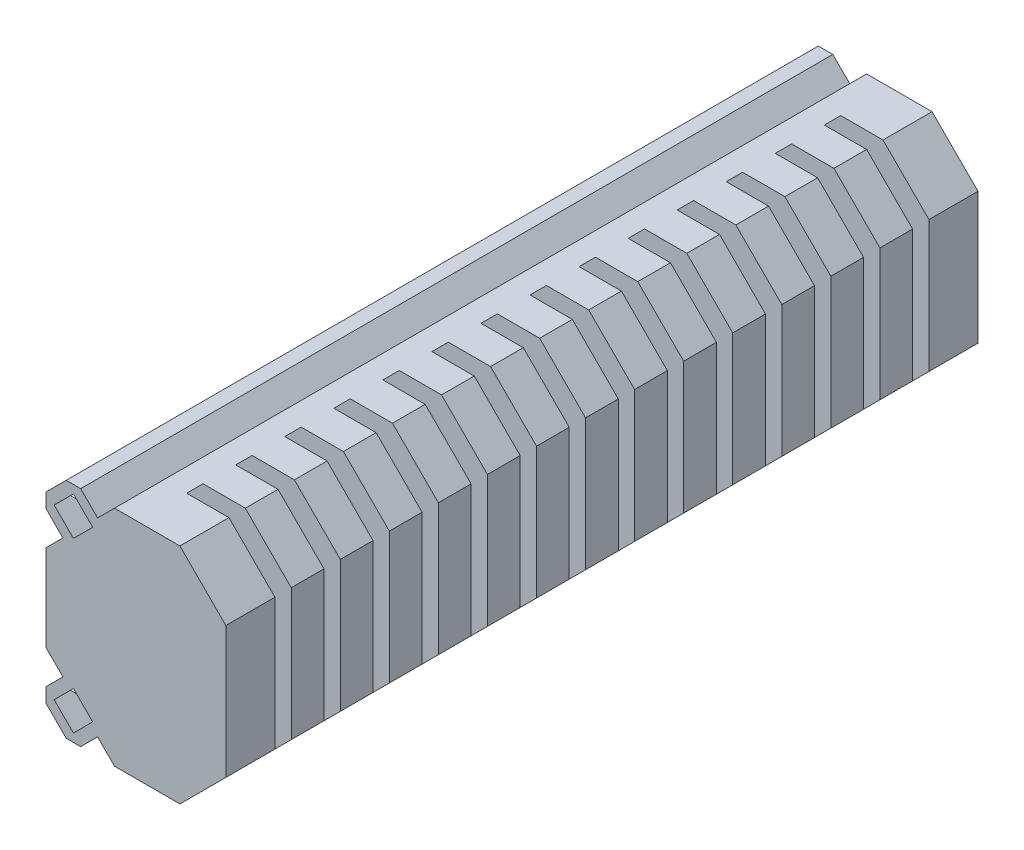
SolidWorks part; units mm, degrees
ref_plane "Ebene vorne" through (0, 0, 0) normal (0, 0, 1) x (1, 0, 0)
ref_plane "Ebene oben" through (0, 0, 0) normal (0, 1, 0) x (1, 0, 0)
ref_plane "Ebene rechts" through (0, 0, 0) normal (1, 0, 0) x (0, 0, -1)
sketch "Skizze3" plane through (0, 0, 0) normal (0, 0, 1) x (1, 0, 0)
  line L0 (-7, 0) -> (0, 7) construction
  line L1 (0, 7) -> (0, -7) construction
  line L2 (0, -7) -> (-7, 0) construction
  line L3 (-7.5, 0) -> (49992.5, 0) construction
  line L4 (-8.2, -3.1716) -> (-8.2, 3.1716)
  line L5 (-8.2, 3.1716) -> (-3.1716, 8.2)
  line L6 (-3.1716, 8.2) -> (1.6284, 8.2)
  line L7 (1.6284, 8.2) -> (5, 4.8284)
  line L13 (0, 7) -> (3, 4) construction
  line L14 (3, 4) -> (3, -4) construction
  line L15 (3, -4) -> (0, -7) construction
  line L16 (5, 4.8284) -> (5, -4.8284)
  line L17 (-8.2, -3.1716) -> (-3.1716, -8.2)
  line L18 (-3.1716, -8.2) -> (1.6284, -8.2)
  line L19 (1.6284, -8.2) -> (5, -4.8284)
  point P20 (-8.2, 0)
  point P23 (5, 0)
  dimension "D2" = 45
  dimension "D3" = 2
  dimension "D4" = 3
  dimension "D5" = 14
  dimension "D1" = 1.2
  dimension "D6" = 2
  dimension "D7" = 1.2
  dimension "D8" = 4.8
extrude "Aufsatz-Linear austragen2" add sketch "Skizze3" along normal mid plane 2.4
sketch "Skizze2" plane through (0, 0, 0) normal (0, 0, 1) x (1, 0, 0)
  line L0 (-7, 0) -> (0, 7)
  line L1 (0, 7) -> (0, -7) construction
  line L2 (0, -7) -> (-7, 0)
  line L3 (-7.5, 0) -> (49992.5, 0) construction
  line L13 (0, 7) -> (3, 4)
  line L14 (3, 4) -> (3, -4)
  line L15 (3, -4) -> (0, -7)
  point P10 (3.1883, -3.4537)
  dimension "D2" = 45
  dimension "D4" = 3
  dimension "D5" = 14
extrude "Schnitt-Linear austragen1" cut sketch "Skizze2" against normal mid plane 0.8
sketch "Skizze5" plane through (0, 0, 0) normal (0, 0, 1) x (1, 0, 0)
  line L0 (-7, 0) -> (-6.1515, 0.8485)
  line L1 (-6.1515, 0.8485) -> (-5.3029, 0)
  line L2 (-5.3029, 0) -> (-6.1515, -0.8485)
  line L3 (-6.1515, -0.8485) -> (-7, 0)
  line L5 (-7, 0) -> (0, -7)
  line L6 (0, -7) -> (3, -4)
  line L7 (3, -4) -> (3, 4)
  line L8 (3, 4) -> (0, 7)
  line L9 (0, 7) -> (-7, 0)
  line L10 (-7, 0) -> (0, -7) construction
  line L11 (0, -7) -> (3, -4) construction
  line L12 (3, -4) -> (3, 4) construction
  line L13 (3, 4) -> (0, 7) construction
  line L14 (0, 7) -> (-7, 0) construction
  point P2 (-5.3661, 0)
  dimension "D2" = 1.2
  dimension "D1" = 0
extrude "Schnitt-Linear austragen2" cut sketch "Skizze5" against normal through all both and the other way through all
sketch "Skizze6" plane through (0, 0, 1.2) normal (0, 0, 1) x (1, 0, 0)
  line L0 (0, 0) -> (50000, 0) construction
  line L1 (1.6284, 8.2) -> (-3.1716, 8.2) construction
  line L3 (-3.1716, 8.2) -> (-8.2, 3.1716) construction
  line L4 (-1.4745, 8.2) -> (-3.1716, 8.2)
  line L5 (-8.2, 3.1716) -> (-8.2, -3.1716)
  line L6 (-3.1716, 8.2) -> (-8.2, 3.1716)
  line L7 (-4.5029, -5.1716) -> (-4.5029, 5.1716)
  line L8 (-4.5029, 5.1716) -> (-1.4745, 8.2)
  line L9 (-8.2, 3.1716) -> (-8.2, -3.1716) construction
  line L10 (-4.5029, -5.1716) -> (-1.4745, -8.2)
  line L11 (-3.1716, -8.2) -> (-8.2, -3.1716)
  line L12 (-1.4745, -8.2) -> (-3.1716, -8.2)
  point P11 (-4.5029, 0)
  point P14 (-8.2, 0)
  dimension "D1" = 1.2
  dimension "D2" = 0.8
extrude "Aufsatz-Linear austragen3" add sketch "Skizze6" along normal blind 1.2
sketch "Skizze7" plane through (0, 0, -1.2) normal (0, 0, -1) x (-1, 0, 0)
  line L4 (6.1515, -0.8485) -> (7, 0)
  line L5 (7, 0) -> (6.1515, 0.8485)
  line L6 (6.1515, 0.8485) -> (5.3029, 0)
  line L7 (5.3029, 0) -> (6.1515, -0.8485)
  line L8 (6.1515, -0.8485) -> (7, 0)
  line L9 (7, 0) -> (6.1515, 0.8485)
  line L10 (6.1515, 0.8485) -> (5.3029, 0)
  line L11 (5.3029, 0) -> (6.1515, -0.8485)
  dimension "D1" = 0
extrude "Schnitt-Linear austragen3" cut sketch "Skizze7" against normal through all
pattern_linear "Lineares Muster1" count 15 spacing 3.6 along (0, 0, 1) of "Aufsatz-Linear austragen2", "Schnitt-Linear austragen1", "Schnitt-Linear austragen2", "Aufsatz-Linear austragen3", "Schnitt-Linear austragen3"
sketch "Skizze8" plane through (0, 0, -1.2) normal (0, 0, -1) x (-1, 0, 0)
  line L8 (3.1716, -8.2) -> (8.2, -3.1716)
  line L9 (8.2, -3.1716) -> (8.2, 3.1716)
  line L10 (8.2, 3.1716) -> (3.1716, 8.2)
  line L11 (3.1716, 8.2) -> (-1.6284, 8.2)
  line L12 (-1.6284, 8.2) -> (-5, 4.8284)
  line L13 (-5, 4.8284) -> (-5, -4.8284)
  line L14 (-5, -4.8284) -> (-1.6284, -8.2)
  line L15 (-1.6284, -8.2) -> (3.1716, -8.2)
  line L16 (3.1716, -8.2) -> (8.2, -3.1716)
  line L17 (8.2, -3.1716) -> (8.2, 3.1716)
  line L18 (8.2, 3.1716) -> (3.1716, 8.2)
  line L19 (3.1716, 8.2) -> (-1.6284, 8.2)
  line L20 (-1.6284, 8.2) -> (-5, 4.8284)
  line L21 (-5, 4.8284) -> (-5, -4.8284)
  line L22 (-5, -4.8284) -> (-1.6284, -8.2)
  line L23 (-1.6284, -8.2) -> (3.1716, -8.2)
  dimension "D1" = 0
extrude "Aufsatz-Linear austragen4" add sketch "Skizze8" along normal blind 1.2 and the other way blind 0.8
sketch "Skizze9" plane through (0, 0, 51.6) normal (0, 0, 1) x (1, 0, 0)
  line L0 (-1.4745, 8.2) -> (-3.1716, 8.2) construction
  line L1 (-3.1716, 8.2) -> (-8.2, 3.1716) construction
  line L2 (-8.2, 3.1716) -> (-8.2, -3.1716) construction
  line L3 (-8.2, -3.1716) -> (-3.1716, -8.2) construction
  line L4 (-3.1716, -8.2) -> (-1.4745, -8.2) construction
  line L5 (-1.4745, 8.2) -> (-3.1716, 8.2)
  line L6 (-3.1716, 8.2) -> (-8.2, 3.1716)
  line L7 (-8.2, 3.1716) -> (-8.2, -3.1716)
  line L8 (-1.4745, 8.2) -> (-4.5029, 5.1716)
  line L9 (-4.5029, 5.1716) -> (-4.5029, -5.1716)
  line L10 (-4.5029, -5.1716) -> (-1.4745, -8.2)
  line L11 (-1.4745, -8.2) -> (1.6284, -8.2)
  line L12 (1.6284, -8.2) -> (5, -4.8284)
  line L13 (5, -4.8284) -> (5, 4.8284)
  line L14 (5, 4.8284) -> (1.6284, 8.2)
  line L15 (1.6284, 8.2) -> (-1.4745, 8.2)
  line L19 (-1.4745, -8.2) -> (1.6284, -8.2)
  line L20 (1.6284, -8.2) -> (5, -4.8284)
  line L21 (5, -4.8284) -> (5, 4.8284)
  line L22 (5, 4.8284) -> (1.6284, 8.2)
  line L23 (1.6284, 8.2) -> (-1.4745, 8.2)
  line L24 (-8.2, -3.1716) -> (-3.1716, -8.2)
  line L25 (-3.1716, -8.2) -> (-1.4745, -8.2)
  dimension "D1" = 0
extrude "Aufsatz-Linear austragen5" add sketch "Skizze9" along normal blind 1.2 and the other way blind 0.8
sketch "Skizze10" plane through (0, 0, -2.4) normal (0, 0, -1) x (-1, 0, 0)
  line L0 (2.1631, -8.2) -> (50002.1631, -8.2) construction
  line L1 (8.2, -2.1493) -> (8.2, -50002.1493) construction
  line L2 (6.1858, -7.6) -> (7.6, -6.1858)
  line L3 (7.6, -6.1858) -> (6.3929, -4.9787)
  line L6 (4.413, -6.9586) -> (5.6544, -8.2)
  line L7 (3.1716, -8.2) -> (8.2, -3.1716) construction
  line L8 (5.6544, -8.2) -> (6.7172, -8.2)
  line L9 (6.7172, -8.2) -> (8.2, -6.7172)
  line L10 (8.2, -6.7172) -> (8.2, -5.6544)
  line L11 (8.2, -5.6544) -> (6.9586, -4.413)
  line L12 (4.413, -6.9586) -> (4.9787, -6.3929)
  line L13 (4.7716, -6.1858) -> (4.2059, -6.7515) construction
  line L14 (7.6, -6.1858) -> (8.1657, -6.7515) construction
  line L15 (6.1858, -4.7716) -> (6.7515, -4.2059) construction
  line L16 (6.9586, -4.413) -> (6.3929, -4.9787)
  line L17 (4.9787, -6.3929) -> (4.7716, -6.1858) construction
  line L18 (4.7716, -6.1858) -> (6.1858, -4.7716) construction
  line L19 (6.1858, -4.7716) -> (6.3929, -4.9787) construction
  line L20 (6.8929, -6.8929) -> (5.4787, -5.4787) construction
  line L21 (4.9787, -6.3929) -> (6.1858, -7.6)
  point P14 (0, 0)
  point P26 (6.7515, -4.2059)
  dimension "D1" = 2
  dimension "D2" = 0.6
  dimension "D3" = 0.6
  dimension "D4" = 0.8
extrude "Aufsatz-Linear austragen6" add sketch "Skizze10" against normal up to surface (55.2 mm away)
sketch "Skizze12" plane through (0, 0, -2.4) normal (0, 0, -1) x (-1, 0, 0)
  line L0 (6.1858, -7.6) -> (4.9787, -6.3929) construction
  line L1 (7.6, -6.1858) -> (6.1858, -7.6) construction
  line L2 (6.3929, -4.9787) -> (7.6, -6.1858) construction
  line L3 (6.1858, -7.6) -> (4.7716, -6.1858)
  line L4 (7.6, -6.1858) -> (6.1858, -7.6)
  line L5 (6.1858, -4.7716) -> (7.6, -6.1858)
  line L6 (6.1858, -4.7716) -> (4.7716, -6.1858)
extrude "Schnitt-Linear austragen5" cut sketch "Skizze12" against normal through all
mirror "Spiegeln1" about plane through (0, 0, 0) normal (0, 1, 0) of "Schnitt-Linear austragen5", "Aufsatz-Linear austragen6"
sketch "Skizze11" plane through (-8.2, 0, 0) normal (-1, 0, 0) x (0, 0, 1)
  line L3 (52.8, 4.7716) -> (-2.4, 4.7716) construction
  line L4 (52.8, 7.6) -> (-2.4, 7.6) construction
  line L5 (52.8, 6.1858) -> (-2.4, 6.1858) construction
  line L6 (-1.2, 6.1858) -> (0.2142, 7.6)
  line L7 (0.2142, 7.6) -> (1.6284, 6.1858)
  line L8 (1.6284, 6.1858) -> (0.2142, 4.7716)
  line L9 (0.2142, 4.7716) -> (-1.2, 6.1858)
  line L10 (-2.4, 6.7172) -> (-2.4, 5.6544) construction
  line L11 (0, 0) -> (50000, 0) construction
  line L12 (25.2, -3.1716) -> (25.2, -50003.1716) construction
  line L13 (52.8, -3.1716) -> (-2.4, -3.1716) construction
  line L14 (0.2142, -4.7716) -> (-1.2, -6.1858)
  line L15 (-1.2, -6.1858) -> (0.2142, -7.6)
  line L16 (0.2142, -7.6) -> (1.6284, -6.1858)
  line L17 (1.6284, -6.1858) -> (0.2142, -4.7716)
  line L18 (48.7716, -6.1858) -> (50.1858, -4.7716)
  line L19 (50.1858, -7.6) -> (48.7716, -6.1858)
  line L20 (51.6, -6.1858) -> (50.1858, -7.6)
  line L21 (50.1858, -4.7716) -> (51.6, -6.1858)
  line L22 (50.1858, 4.7716) -> (51.6, 6.1858)
  line L23 (51.6, 6.1858) -> (50.1858, 7.6)
  line L24 (50.1858, 7.6) -> (48.7716, 6.1858)
  line L25 (48.7716, 6.1858) -> (50.1858, 4.7716)
  line L26 (52.8, 4.7716) -> (-2.4, 4.7716) construction
  line L27 (52.8, 7.6) -> (-2.4, 7.6) construction
  line L28 (52.8, 6.1858) -> (-2.4, 6.1858) construction
  circle A0 centre (50.1858, 6.7515) radius 0.6 construction
  point P19 (25.2, -3.1716)
  point P20 (0, 0)
  point P35 (0, 0)
  point P36 (0, 0)
  point P37 (0, 0)
  dimension "D2" = 1.2
  dimension "D1" = 1.2
extrude "Schnitt-Linear austragen4" cut sketch "Skizze11" against normal up to next
